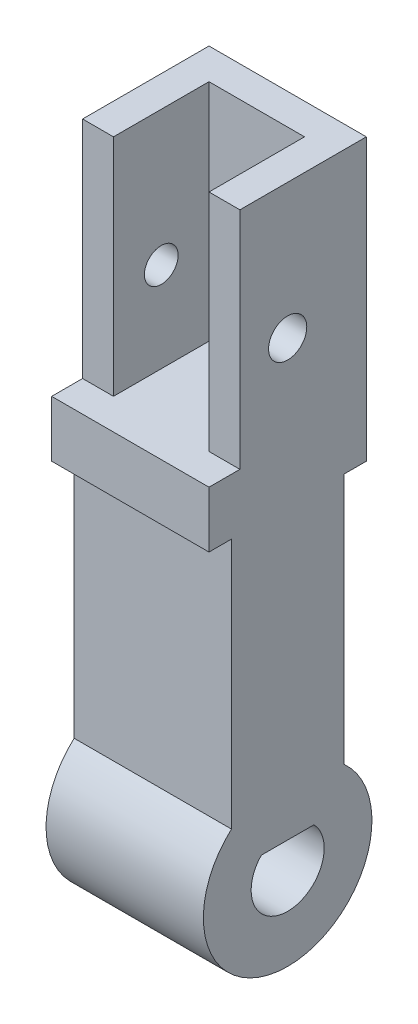
SolidWorks part; units mm, degrees
material "PLA"
ref_plane "Plan de face" through (0, 0, 0) normal (0, 0, 1) x (1, 0, 0)
ref_plane "Plan de dessus" through (0, 0, 0) normal (0, 1, 0) x (1, 0, 0)
ref_plane "Plan de droite" through (0, 0, 0) normal (1, 0, 0) x (0, 0, -1)
sketch "Esquisse1" plane through (0, 0, 0) normal (0, 0, 1) x (1, 0, 0)
  line L1 (0, 0) -> (140, 0) construction
  line L2 (0, 0) -> (0, 155) construction
  line L3 (0, 155) -> (140, 155) construction
  line L4 (140, 0) -> (140, 155) construction
  line L16 (65, 0) -> (65, 121.945)
  line L17 (65, 121.945) -> (0, 145.6031)
  line L18 (0, 145.6031) -> (3.4202, 155)
  line L19 (3.4202, 155) -> (70, 130.7669)
  line L20 (70, 130.7669) -> (136.5798, 155)
  line L21 (136.5798, 155) -> (140, 145.6031)
  line L22 (140, 145.6031) -> (75, 121.945)
  line L23 (75, 121.945) -> (75, 0)
  line L24 (75, 0) -> (65, 0)
  point P19 (70, 0)
  dimension "D1" = 140
  dimension "D2" = 155
  dimension "D3" = 10
  dimension "D4" = 70
  dimension "D5" = 110
  dimension "D6" = 110
  dimension "D7" = 140
  dimension "D8" = 10
  dimension "D9" = 10
  dimension "D10" = 70
extrude "Boss.-Extru.1" add sketch "Esquisse1" along normal blind 10
sketch "Esquisse2" plane through (0, 0, 0) normal (0, 0, -1) x (-1, 0, 0)
  line L0 (-75, 121.945) -> (-140, 145.6031) construction
  line L1 (-140, 145.6031) -> (-136.5798, 155) construction
  line L2 (-136.5798, 155) -> (-70, 130.7669) construction
  line L3 (-135.3015, 143.893) -> (-140, 145.6031)
  line L4 (-140, 145.6031) -> (-136.5798, 155)
  line L5 (-136.5798, 155) -> (-127.1829, 151.5798)
  line L6 (-128.893, 146.8813) -> (-127.1829, 151.5798)
  line L7 (0, 145.6031) -> (-65, 121.945) construction
  line L8 (-70, 130.7669) -> (-3.4202, 155) construction
  line L9 (-3.4202, 155) -> (0, 145.6031) construction
  line L10 (0, 145.6031) -> (-4.6985, 143.893)
  line L11 (-12.8171, 151.5798) -> (-3.4202, 155)
  line L12 (-3.4202, 155) -> (0, 145.6031)
  line L13 (-12.8171, 151.5798) -> (-11.107, 146.8813)
  line L14 (-135.3015, 143.893) -> (-128.893, 146.8813)
  line L15 (-11.107, 146.8813) -> (-4.6985, 143.893)
  dimension "D1" = 10
  dimension "D2" = 10
  dimension "D3" = 5
  dimension "D4" = 5
  dimension "D5" = 5
  dimension "D6" = 5
extrude "Boss.-Extru.2" add sketch "Esquisse2" along normal blind 15
fillet "Congé1" radius 20 3 edges at (75, 121.945, 5) (65, 121.945, 5) (70, 130.7669, 5)
fillet "Congé2" radius 4 2 edges at (138.2899, 150.3015, 10) (1.7101, 150.3015, 10)
sketch "Esquisse3" plane through (65, 0, 0) normal (-1, 0, 0) x (0, 0, 1)
  line L0 (5, 0) -> (5, 33.6289) construction
  line L1 (10, 0) -> (0, 0) construction
  circle A0 centre (5, 0) radius 7.5
  dimension "D1" = 15
extrude "Boss.-Extru.3" add sketch "Esquisse3" against normal up to surface (10 mm away) up to face at (75, 53.9704, 5)
sketch "Esquisse7" plane through (0, 0, 10) normal (0, 0, 1) x (1, 0, 0)
  line L0 (3.4202, 155) -> (0, 145.6031)
  line L1 (0, 145.6031) -> (51.8404, 126.7347)
  line L2 (65, 107.9409) -> (65, 27.9409)
  line L3 (65, 107.9409) -> (65, 5.5902) construction
  line L4 (65, 27.9409) -> (75, 27.9409)
  line L5 (75, 5.5902) -> (75, 107.9409) construction
  line L6 (75, 27.9409) -> (75, 107.9409)
  line L7 (88.1596, 126.7347) -> (140, 145.6031)
  line L8 (140, 145.6031) -> (136.5798, 155)
  line L9 (136.5798, 155) -> (76.8404, 133.2566)
  line L10 (63.1596, 133.2566) -> (3.4202, 155)
  arc A0 (51.8404, 126.7347) -> (65, 107.9409) centre (45, 107.9409) cw
  arc A1 (75, 107.9409) -> (88.1596, 126.7347) centre (95, 107.9409) cw
  arc A2 (76.8404, 133.2566) -> (63.1596, 133.2566) centre (70, 152.0505) cw
  dimension "D1" = 80
extrude "Enlèv. mat.-Extru.1" cut sketch "Esquisse7" against normal up to surface (25 mm away) up to face at (133.5914, 148.5914, -15)
sketch "Esquisse11" plane through (0, 27.9409, 0) normal (0, 1, 0) x (1, 0, 0)
  line L0 (65, 0) -> (65, -10) construction
  line L1 (61, 2) -> (75, 2)
  line L2 (61, 2) -> (61, -12)
  line L3 (61, -12) -> (75, -12)
  line L4 (75, 2) -> (75, -12)
  line L5 (65, -10) -> (75, -10) construction
  dimension "D1" = 14
  dimension "D2" = 14
  dimension "D3" = 4
  dimension "D4" = 2
extrude "Boss.-Extru.4" add sketch "Esquisse11" along normal blind 25
sketch "Esquisse12" plane through (0, 52.9409, 0) normal (0, 1, 0) x (1, 0, 0)
  line L0 (68, 2) -> (68, -12) construction
  line L1 (63.75, -0.75) -> (72.25, -0.75)
  line L2 (63.75, -0.75) -> (63.75, -9.25)
  line L3 (63.75, -9.25) -> (72.25, -9.25)
  line L4 (72.25, -0.75) -> (72.25, -9.25)
  line L5 (75, 2) -> (61, 2) construction
  line L6 (61, -12) -> (75, -12) construction
  line L7 (61, -5) -> (75, -5) construction
  line L8 (61, 2) -> (61, -12) construction
  line L9 (75, -12) -> (75, 2) construction
  line L10 (68, -0.75) -> (68, -9.25) construction
  line L11 (63.75, -5) -> (72.25, -5) construction
  dimension "D1" = 8.5
  dimension "D2" = 8.5
extrude "Enlèv. mat.-Extru.4" cut sketch "Esquisse12" against normal blind 20
sketch "Esquisse13" plane through (61, 0, 0) normal (-1, 0, 0) x (0, 0, 1)
  line L2 (12, 52.9409) -> (12, 27.9409) construction
  line L3 (-2, 52.9409) -> (12, 52.9409) construction
  circle A0 centre (5, 40.9409) radius 1.5
  dimension "D3" = 3
  dimension "D1" = 12
  dimension "D2" = 7
extrude "Enlèv. mat.-Extru.5" cut sketch "Esquisse13" against normal up to surface (14 mm away) up to face at (75, 26.9669, 5)
sketch "Esquisse4" plane through (65, 0, 0) normal (-1, 0, 0) x (0, 0, 1)
  line L7 (5, 0) -> (5, 7.4852) construction
  line L11 (2.6548, 2.25) -> (7.3452, 2.25)
  line L12 (0.3981, -3.25) -> (8.2082, -3.25) construction
  arc A1 (2.6548, 2.25) -> (7.3452, 2.25) centre (5, 0) ccw
  point P10 (5, 6)
  point P11 (5, 6)
  dimension "D1" = 6.5
  dimension "D2" = 5.5
extrude "Enlèv. mat.-Extru.2" cut sketch "Esquisse4" against normal blind 20
sketch "Esquisse15" plane through (0, 0, 12) normal (0, 0, 1) x (1, 0, 0)
  line L0 (75, 52.9409) -> (75, 27.9409) construction
  line L1 (61, 52.9409) -> (75, 52.9409) construction
  line L2 (61, 27.9409) -> (75, 27.9409) construction
  circle A1 centre (68, 45.9409) radius 1.5
  circle A2 centre (68, 35.9409) radius 1.5
  dimension "D5" = 3
  dimension "D6" = 3
  dimension "D1" = 7
  dimension "D2" = 7
  dimension "D3" = 7
  dimension "D4" = 8
extrude "Enlèv. mat.-Extru.6" cut sketch "Esquisse15" against normal up to surface (14 mm away) up to face at (68, 40.4409, -2)
hole_wizard "Dégagement M31" positions "Esquisse16" profile "Esquisse17" hole size "M3" standard "ISO"
sketch "Esquisse16" plane through (0, 0, -2) normal (0, 0, -1) x (-1, 0, 0)
  point P0 (-68, 45.9409)
  point P3 (-68, 35.9409)
sketch "Esquisse17" plane through (68, 45.9409, -2) normal (1, 0, 0) x (0, 1, 0)
  line L0 (0, 0) -> (0, 11.0215)
  line L1 (0, 11.0215) -> (1.7, 10)
  line L2 (1.7, 10) -> (1.7, 0)
  line L5 (1.7, 0) -> (0, 0)
  line L10 (0, 11.0215) -> (-1.7, 10) construction
  line L11 (0, -6.35) -> (0, 107.95) construction
  dimension "Diamètre du perçage" = 3.4
  dimension "Profondeur du perçage" = 10
  dimension "Angle de pointe" = 118
hole_wizard "Dégagement M32" positions "Esquisse18" profile "Esquisse19" hole size "M3" standard "ISO"
sketch "Esquisse18" plane through (75, 0, 0) normal (1, 0, 0) x (0, 0, -1)
  point P0 (-5, 40.9409)
sketch "Esquisse19" plane through (75, 40.9409, 5) normal (0, 1, 0) x (0, 0, -1)
  line L0 (0, 0) -> (0, 11.0215)
  line L1 (0, 11.0215) -> (1.7, 10)
  line L2 (1.7, 10) -> (1.7, 0)
  line L5 (1.7, 0) -> (0, 0)
  line L10 (0, 11.0215) -> (-1.7, 10) construction
  line L11 (0, -6.35) -> (0, 107.95) construction
  dimension "Diamètre du perçage" = 3.4
  dimension "Profondeur du perçage" = 10
  dimension "Angle de pointe" = 118
sketch "Esquisse20" plane through (65, 0, 0) normal (-1, 0, 0) x (0, 0, 1)
  line L0 (10, 5.5902) -> (10, 27.9409)
  line L1 (-2, 27.9409) -> (12, 27.9409) construction
  line L2 (10, 27.9409) -> (10, 5.5902) construction
  line L3 (10, 27.9409) -> (0, 27.9409)
  line L4 (0, 27.9409) -> (0, 5.5902)
  line L5 (7.3452, 2.25) -> (2.6548, 2.25)
  arc A0 (0, 5.5902) -> (10, 5.5902) centre (5, 0) ccw
  arc A1 (2.6548, 2.25) -> (7.3452, 2.25) centre (5, 0) ccw
extrude "Boss.-Extru.6" add sketch "Esquisse20" along normal blind 4
sketch "Esquisse21" plane through (0, 52.9409, 0) normal (0, 1, 0) x (1, 0, 0)
  line L6 (75, -12) -> (75, 2) construction
  line L7 (61, -12) -> (75, -12)
  line L8 (61, -12) -> (61, -9.25)
  line L9 (61, -9.25) -> (75, -9.25)
  line L10 (75, -12) -> (75, -9.25)
  line L11 (63.75, -9.25) -> (72.25, -9.25) construction
extrude "Enlèv. mat.-Extru.7" cut sketch "Esquisse21" against normal blind 20
equation "\"long_tot\"=155"
equation "\"espac_sub_arms\"= 120"
equation "\"épaiss_cadre\"=10"
equation "\"long_protub\"= 15"
equation "\"rayon_conge\"= 3"
equation "\"diam_axe\"= 5"
equation "\"D1@Esquisse1\"=\"espac_sub_arms\"+\"épaiss_cadre\"*2"
equation "\"D2@Esquisse1\"=\"long_tot\""
equation "\"D3@Esquisse1\"=\"épaiss_cadre\""
equation "\"D4@Esquisse1\"=\"D1@Esquisse1\"/2"
equation "\"D6@Esquisse1\"=\"D5@Esquisse1\""
equation "\"D8@Esquisse1\"=\"épaiss_cadre\""
equation "\"D9@Esquisse1\"=\"épaiss_cadre\""
equation "\"D10@Esquisse1\"=\"D4@Esquisse1\""
equation "\"D1@Boss.-Extru.1\"=\"épaiss_cadre\""
equation "\"D2@Esquisse2\"=\"épaiss_cadre\""
equation "\"D1@Boss.-Extru.2\"=\"long_protub\""
equation "\"D1@Esquisse2\"=\"épaiss_cadre\""
equation "\"D3@Esquisse2\"=\"D1@Esquisse2\"/2"
equation "\"D4@Esquisse2\"=\"D1@Esquisse2\"/2"
equation "\"D5@Esquisse2\"=\"D2@Esquisse2\"/2"
equation "\"D6@Esquisse2\"=\"D2@Esquisse2\"/2"
